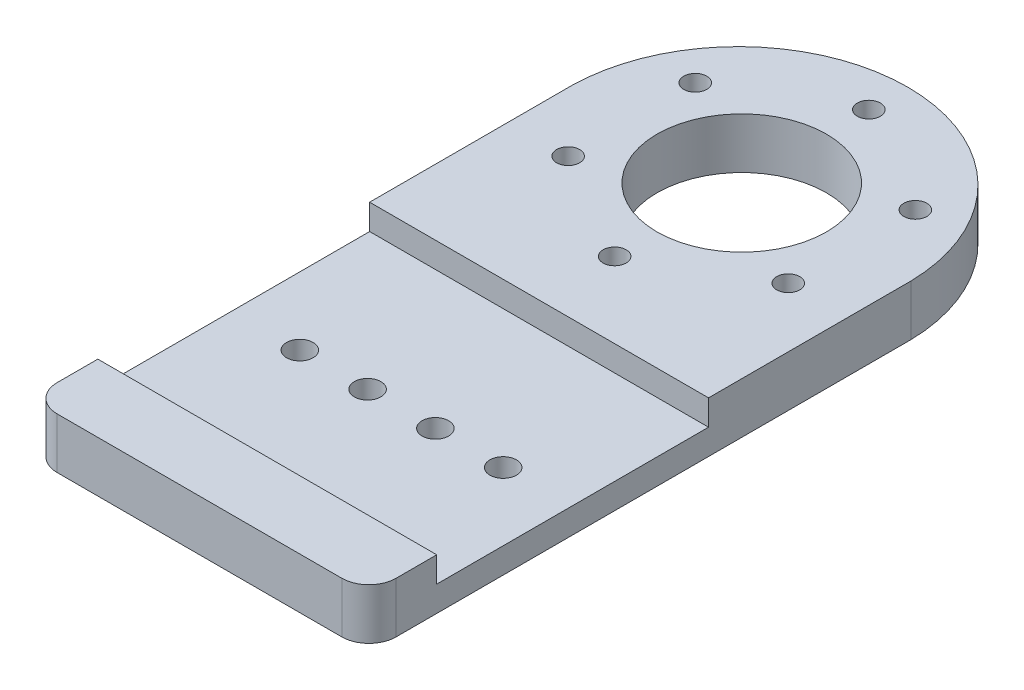
SolidWorks part; units mm, degrees
ref_plane "Front Plane" through (0, 0, 0) normal (0, 0, 1) x (1, 0, 0)
ref_plane "Top Plane" through (0, 0, 0) normal (0, 1, 0) x (1, 0, 0)
ref_plane "Right Plane" through (0, 0, 0) normal (1, 0, 0) x (0, 0, -1)
sketch "Sketch1" plane through (0, 0, 0) normal (0, 1, 0) x (1, 0, 0)
  line L0 (0, -111.3091) -> (63.5, -111.3091)
  line L2 (0, -22.4091) -> (0, -124.0091)
  line L3 (0, -124.0091) -> (63.5, -124.0091)
  line L4 (63.5, -22.4091) -> (63.5, -124.0091)
  line L5 (0, -9.7091) -> (50000, -9.7091) construction
  line L6 (31.75, -22.4091) -> (-49968.25, -22.4091) construction
  line L7 (0, -60.3821) -> (63.5, -60.3821)
  circle A0 centre (31.75, -22.4091) radius 15.875
  circle A1 centre (12.7, -86.1631) radius 2.4892
  circle A2 centre (25.4, -86.1631) radius 2.4892
  circle A3 centre (38.1, -86.1631) radius 2.4892
  circle A4 centre (50.8, -86.1631) radius 2.4892
  arc A8 (63.5, -22.4091) -> (0, -22.4091) centre (31.75, -23.0483) ccw
  point P25 (63.5, -9.7091)
  dimension "D3" = 31.75
  dimension "D5" = 31.75
  dimension "D6" = 4.9784
  dimension "D7" = 12.7
  dimension "D8" = 37.846
  dimension "D10" = 12.7
  dimension "D12" = 63.627
  dimension "D9" = 4
extrude "Boss-Extrude2" add sketch "Sketch1" along normal blind 9.525 contours L4 L0 L2 L3 | L2 L7 L4 A0 | L5 A0 region at (31.75, 0, 117.6591) region at (0.9384, 0, 41.3956)
extrude "Boss-Extrude3" add sketch "Sketch1<3>" along normal blind 4.7625 contours L7 L2 L0 L4 A4 A3 A2 A1 region at (31.75, 0, 85.8377)
sketch "Sketch1<3>" plane through (0, 0, 0) normal (0, 1, 0) x (1, 0, 0) same geometry as "Sketch1"
sketch "Sketch2" plane through (0, 0, 0) normal (0, -1, 0) x (1, 0, 0)
  line L0 (31.75, 22.4091) -> (11.1278, 34.3153) construction
  line L1 (31.75, 22.4091) -> (31.75, 46.2216) construction
  circle A0 centre (11.1278, 34.3153) radius 2.159
  circle A4 centre (31.75, 22.4091) radius 23.8125 construction
  circle A5 centre (31.75, 46.2216) radius 2.159
  circle A6 centre (52.3722, 34.3153) radius 2.159
  circle A7 centre (52.3722, 10.5028) radius 2.159
  circle A8 centre (31.75, -1.4034) radius 2.159
  circle A9 centre (11.1278, 10.5028) radius 2.159
  point P2 (0, 0)
  point P3 (0, 0)
  point P4 (0, 0)
  dimension "D1" = 4.318
  dimension "D3" = 60
  dimension "D4" = 47.625
  dimension "D2" = 6
extrude "Cut-Extrude1" cut sketch "Sketch2" against normal through all
sketch "Sketch3" plane through (0, 0, 0) normal (0, -1, 0) x (1, 0, 0)
  line L0 (-939.958, 124.0091) -> (49060.042, 124.0091) construction
  line L2 (63.5, -875.9909) -> (63.5, 49124.0091) construction
  point P3 (63.5, 124.0091)
fillet "Fillet1" radius 5.08 2 edges at (0, 4.7625, 124.0091) (63.5, 4.7625, 124.0091)
